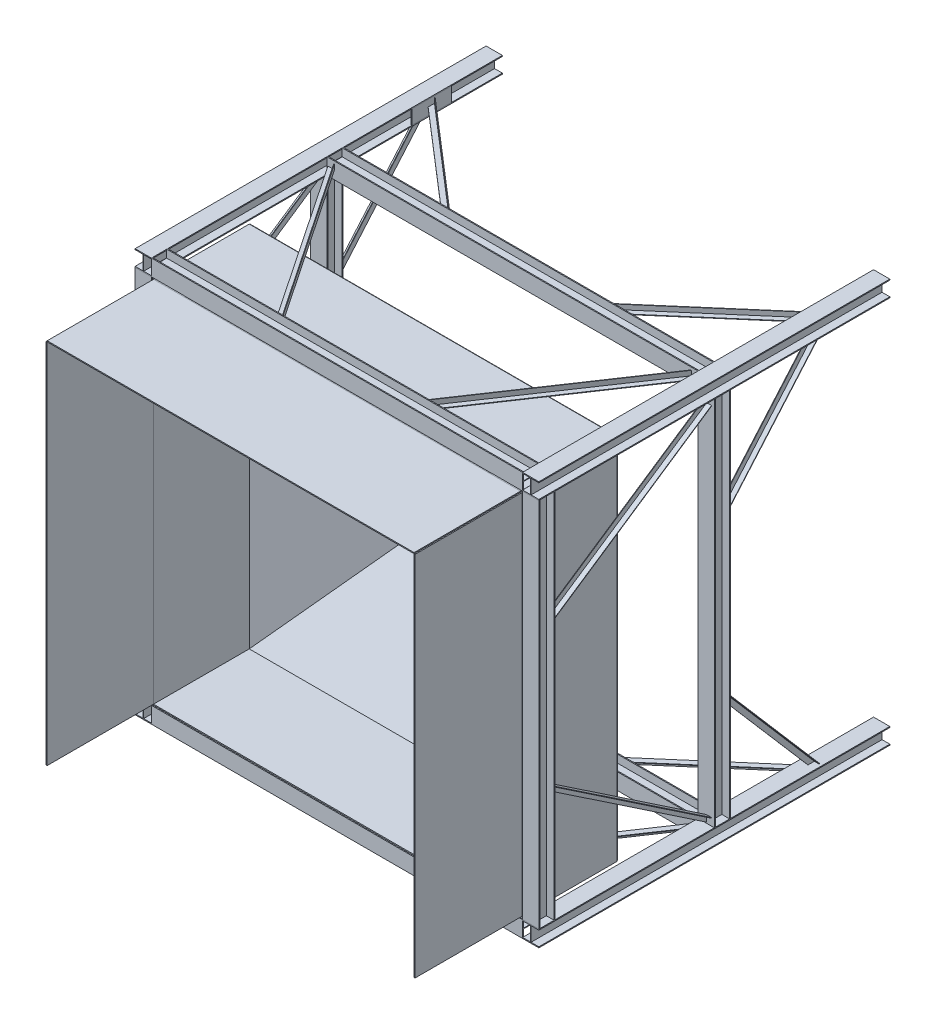
SolidWorks part; units mm, degrees
other "DetailItem1"
other "DetailItem2"
other "DetailItem3"
other "DetailItem4"
other "DetailItem5"
other "DetailItem6"
other "DetailItem7"
other "DetailItem8"
other "DetailItem9"
other "DetailItem10"
other "DetailItem11"
other "DetailItem12"
other "DetailItem13"
other "DetailItem14"
other "DetailItem15"
other "DetailItem16"
other "DetailItem17"
other "DetailItem18"
other "DetailItem19"
other "DetailItem20"
other "DetailItem21"
other "DetailItem22"
other "DetailItem23"
other "DetailItem24"
other "DetailItem25"
other "DetailItem26"
other "DetailItem27"
other "DetailItem28"
other "DetailItem29"
other "DetailItem30"
other "DetailItem31"
other "DetailItem32"
other "DetailItem33"
other "DetailItem34"
other "DetailItem35"
other "DetailItem36"
other "DetailItem37"
other "DetailItem38"
other "DetailItem39"
other "DetailItem40"
other "DetailItem41"
other "DetailItem42"
other "DetailItem43"
other "DetailItem44"
other "DetailItem45"
other "DetailItem46"
other "DetailItem47"
other "DetailItem48"
other "DetailItem49"
other "DetailItem50"
other "DetailItem51"
other "DetailItem52"
other "DetailItem53"
other "DetailItem54"
other "DetailItem55"
other "DetailItem56"
other "DetailItem57"
other "DetailItem58"
other "DetailItem59"
other "DetailItem60"
other "DetailItem61"
other "DetailItem62"
other "DetailItem63"
other "DetailItem64"
other "DetailItem65"
other "DetailItem66"
other "DetailItem67"
other "DetailItem68"
other "DetailItem69"
other "DetailItem70"
other "DetailItem71"
other "DetailItem72"
other "DetailItem73"
other "Carpeta de soldadura"
other "Cordón de soldadura1"
other "Soldadura Viga H carga 1650 B"
other "Soldadura Viga H carga 3300 A"
other "Soldadura Viga H carga 3300 B"
other "Soldadura asiento a tolva carga"
other "Soldadura asiento a bastidor carga"
other "Soldadura Viga H fondo 1650 A"
other "Soldadura Viga H fondo 1650 B"
other "Soldadura Viga H fondo 3300 A"
other "Soldadura Viga H fondo 3300 B"
other "Soldadura asiento a tolva fondo"
other "Soldadura asiento a bastidor fondo"
other "Soldadura Viga H izquierda 1650 A"
other "Soldadura Viga H izquierda 1650 B"
other "Soldadura Viga H izquierda 3300 A"
other "Soldadura Viga H izquierda 3300 B"
other "Soldadura asiento a tolva izquierda"
other "Soldadura asiento a bastidor izquierda"
other "Soldadura Viga H derecha 1650 A"
other "Soldadura Viga H derecha 1650 B"
other "Soldadura Viga H derecha 3300 A"
other "Soldadura Viga H derecha 3300 B"
other "Soldadura asiento a tolva derecha"
other "Soldadura asiento a bastidor derecha"
other "Soldadura Angular superior carga A inferior"
other "Soldadura Angular superior carga A superior"
other "Soldadura Angular inferior carga A inferior"
other "Soldadura Angular inferior carga A superior"
other "Soldadura Angular superior carga B inferior"
other "Soldadura Angular superior carga B superior"
other "Soldadura Angular inferior carga B inferior"
other "Soldadura Angular inferior carga B superior"
other "Soldadura Angular superior fondo A inferior"
other "Soldadura Angular superior fondo A superior"
other "Soldadura Angular inferior fondo A inferior"
other "Soldadura Angular inferior fondo A superior"
other "Soldadura Angular superior fondo B inferior"
other "Soldadura Angular superior fondo B superior"
other "Soldadura Angular inferior fondo B inferior"
other "Soldadura Angular inferior fondo B superior"
other "Soldadura Angular superior izquierda A inferior"
other "Soldadura Angular superior izquierda A superior"
other "Soldadura Angular inferior izquierda A inferior"
other "Soldadura Angular inferior izquierda A superior"
other "Soldadura Angular superior izquierda B inferior"
other "Soldadura Angular superior izquierda B superior"
other "Soldadura Angular inferior izquierda B inferior"
other "Soldadura Angular inferior izquierda B superior"
other "Soldadura Angular superior derecha A inferior"
other "Soldadura Angular superior derecha A superior"
other "Soldadura Angular inferior derecha A inferior"
other "Soldadura Angular inferior derecha A superior"
other "Soldadura Angular superior derecha B inferior"
other "Soldadura Angular superior derecha B superior"
other "Soldadura Angular inferior derecha B inferior"
other "Soldadura Angular inferior derecha B superior"
other "Soldadura esquina del collar carga"
other "Soldadura quiebre del embudo carga"
other "Soldadura arista inclinada carga"
other "Soldadura alerón a collar derecha"
other "Soldadura esquina del collar derecha"
other "Soldadura quiebre del embudo derecha"
other "Soldadura arista inclinada derecha"
other "Soldadura alerón a collar fondo"
other "Soldadura esquina del collar fondo"
other "Soldadura quiebre del embudo fondo"
other "Soldadura arista inclinada fondo"
other "Soldadura alerón a collar izquierda"
other "Soldadura esquina del collar izquierda"
other "Soldadura quiebre del embudo izquierda"
other "Soldadura arista inclinada izquierda"
other "Soldadura esquina alerones derecha"
other "Soldadura esquina alerones izquierda"
material "ASTM A36 Steel"
ref_plane "Front Plane" through (0, 0, 0) normal (0, 0, 1) x (1, 0, 0)
ref_plane "Top Plane" through (0, 0, 0) normal (0, 1, 0) x (1, 0, 0)
ref_plane "Right Plane" through (0, 0, 0) normal (1, 0, 0) x (0, 0, -1)
sketch3d "Referencias 1"
  point P0 (0, 0, 0)
  point P1 (0, -190, 0)
  point P2 (200, 0, 0)
ref_plane "Plano de perfil 1 estructura" through (0, 0, 0) normal (0, 0, 1) x (1, 0, 0)
sketch "Contorno Columna H 1" plane through (0, 0, 0) normal (0, 0, 1) x (1, 0, 0)
  line L0 (-1898, -1898) -> (-1745, -1898)
  line L1 (-1745, -1898) -> (-1745, -1889)
  line L2 (-1745, -1889) -> (-1818.25, -1889)
  line L3 (-1818.25, -1889) -> (-1818.25, -1754)
  line L4 (-1818.25, -1754) -> (-1745, -1754)
  line L5 (-1745, -1754) -> (-1745, -1745)
  line L6 (-1745, -1745) -> (-1898, -1745)
  line L7 (-1898, -1745) -> (-1898, -1754)
  line L8 (-1898, -1754) -> (-1824.75, -1754)
  line L9 (-1824.75, -1754) -> (-1824.75, -1889)
  line L10 (-1824.75, -1889) -> (-1898, -1889)
  line L11 (-1898, -1889) -> (-1898, -1898)
extrude "Columna H 1" add sketch "Contorno Columna H 1" along normal blind 3300 separate body
sketch "Contorno Columna H 2" plane through (0, 0, 0) normal (0, 0, 1) x (1, 0, 0)
  line L0 (-1898, 1745) -> (-1745, 1745)
  line L1 (-1745, 1745) -> (-1745, 1754)
  line L2 (-1745, 1754) -> (-1818.25, 1754)
  line L3 (-1818.25, 1754) -> (-1818.25, 1889)
  line L4 (-1818.25, 1889) -> (-1745, 1889)
  line L5 (-1745, 1889) -> (-1745, 1898)
  line L6 (-1745, 1898) -> (-1898, 1898)
  line L7 (-1898, 1898) -> (-1898, 1889)
  line L8 (-1898, 1889) -> (-1824.75, 1889)
  line L9 (-1824.75, 1889) -> (-1824.75, 1754)
  line L10 (-1824.75, 1754) -> (-1898, 1754)
  line L11 (-1898, 1754) -> (-1898, 1745)
extrude "Columna H 2" add sketch "Contorno Columna H 2" along normal blind 3300 separate body
sketch "Contorno Columna H 3" plane through (0, 0, 0) normal (0, 0, 1) x (1, 0, 0)
  line L0 (1745, -1898) -> (1898, -1898)
  line L1 (1898, -1898) -> (1898, -1889)
  line L2 (1898, -1889) -> (1824.75, -1889)
  line L3 (1824.75, -1889) -> (1824.75, -1754)
  line L4 (1824.75, -1754) -> (1898, -1754)
  line L5 (1898, -1754) -> (1898, -1745)
  line L6 (1898, -1745) -> (1745, -1745)
  line L7 (1745, -1745) -> (1745, -1754)
  line L8 (1745, -1754) -> (1818.25, -1754)
  line L9 (1818.25, -1754) -> (1818.25, -1889)
  line L10 (1818.25, -1889) -> (1745, -1889)
  line L11 (1745, -1889) -> (1745, -1898)
extrude "Columna H 3" add sketch "Contorno Columna H 3" along normal blind 3300 separate body
sketch "Contorno Columna H 4" plane through (0, 0, 0) normal (0, 0, 1) x (1, 0, 0)
  line L0 (1745, 1745) -> (1898, 1745)
  line L1 (1898, 1745) -> (1898, 1754)
  line L2 (1898, 1754) -> (1824.75, 1754)
  line L3 (1824.75, 1754) -> (1824.75, 1889)
  line L4 (1824.75, 1889) -> (1898, 1889)
  line L5 (1898, 1889) -> (1898, 1898)
  line L6 (1898, 1898) -> (1745, 1898)
  line L7 (1745, 1898) -> (1745, 1889)
  line L8 (1745, 1889) -> (1818.25, 1889)
  line L9 (1818.25, 1889) -> (1818.25, 1754)
  line L10 (1818.25, 1754) -> (1745, 1754)
  line L11 (1745, 1754) -> (1745, 1745)
extrude "Columna H 4" add sketch "Contorno Columna H 4" along normal blind 3300 separate body
sketch3d "Referencias 2"
  point P0 (-1745, 0, 0)
  point P1 (-1745, 190, 0)
  point P2 (-1745, 0, 200)
ref_plane "Plano de perfil 2 estructura" through (-1745, 0, 0) normal (1, 0, 0) x (0, 0, -1)
sketch "Contorno Viga H carga 1650" plane through (-1745, 0, 0) normal (1, 0, 0) x (0, 0, -1)
  line L0 (-1497, -1745) -> (-1497, -1898)
  line L1 (-1497, -1898) -> (-1506, -1898)
  line L2 (-1506, -1898) -> (-1506, -1824.75)
  line L3 (-1506, -1824.75) -> (-1641, -1824.75)
  line L4 (-1641, -1824.75) -> (-1641, -1898)
  line L5 (-1641, -1898) -> (-1650, -1898)
  line L6 (-1650, -1898) -> (-1650, -1745)
  line L7 (-1650, -1745) -> (-1641, -1745)
  line L8 (-1641, -1745) -> (-1641, -1818.25)
  line L9 (-1641, -1818.25) -> (-1506, -1818.25)
  line L10 (-1506, -1818.25) -> (-1506, -1745)
  line L11 (-1506, -1745) -> (-1497, -1745)
extrude "Viga H carga 1650" add sketch "Contorno Viga H carga 1650" along normal blind 3490 separate body
sketch "Contorno Viga H carga 3300" plane through (-1745, 0, 0) normal (1, 0, 0) x (0, 0, -1)
  line L0 (-3147, -1745) -> (-3147, -1898)
  line L1 (-3147, -1898) -> (-3156, -1898)
  line L2 (-3156, -1898) -> (-3156, -1824.75)
  line L3 (-3156, -1824.75) -> (-3291, -1824.75)
  line L4 (-3291, -1824.75) -> (-3291, -1898)
  line L5 (-3291, -1898) -> (-3300, -1898)
  line L6 (-3300, -1898) -> (-3300, -1745)
  line L7 (-3300, -1745) -> (-3291, -1745)
  line L8 (-3291, -1745) -> (-3291, -1818.25)
  line L9 (-3291, -1818.25) -> (-3156, -1818.25)
  line L10 (-3156, -1818.25) -> (-3156, -1745)
  line L11 (-3156, -1745) -> (-3147, -1745)
extrude "Viga H carga 3300" add sketch "Contorno Viga H carga 3300" along normal blind 3490 separate body
sketch "Contorno Cierre columna carga A" plane through (-1745, 0, 0) normal (1, 0, 0) x (0, 0, -1)
  line L0 (-480, -1754) -> (-480, -1889)
  line L1 (-480, -1889) -> (-850, -1889)
  line L2 (-850, -1889) -> (-850, -1754)
  line L3 (-850, -1754) -> (-480, -1754)
extrude "Cierre columna carga A" add sketch "Contorno Cierre columna carga A" against normal blind 8 separate body
sketch3d "Referencias 3"
  point P0 (0, -1821.5, 0)
  point P1 (-190, -1821.5, 0)
  point P2 (0, -1821.5, 200)
ref_plane "Plano de perfil 3 estructura" through (0, -1821.5, 0) normal (0, 1, 0) x (1, 0, 0)
sketch "Contorno Ala plana Angular superior carga A" plane through (0, -1821.5, 0) normal (0, 1, 0) x (1, 0, 0)
  line L0 (-1674.8701, -1650) -> (-1735.1299, -1650)
  line L1 (-1735.1299, -1650) -> (-728.1299, -3147)
  line L2 (-728.1299, -3147) -> (-667.8701, -3147)
  line L3 (-667.8701, -3147) -> (-1674.8701, -1650)
extrude "Ala plana Angular superior carga A" add sketch "Contorno Ala plana Angular superior carga A" against normal blind 5 separate body
sketch3d "Referencias 4"
  point P0 (0, -1826.5, 0)
  point P1 (-190, -1826.5, 0)
  point P2 (0, -1826.5, 200)
ref_plane "Plano de perfil 4 estructura" through (0, -1826.5, 0) normal (0, 1, 0) x (1, 0, 0)
sketch "Contorno Retorno Angular superior carga A" plane through (0, -1826.5, 0) normal (0, 1, 0) x (1, 0, 0)
  line L0 (-1674.8701, -1650) -> (-1680.8961, -1650)
  line L1 (-1680.8961, -1650) -> (-673.8961, -3147)
  line L2 (-673.8961, -3147) -> (-667.8701, -3147)
  line L3 (-667.8701, -3147) -> (-1674.8701, -1650)
extrude "Retorno Angular superior carga A" add sketch "Contorno Retorno Angular superior carga A" against normal blind 45 separate body
combine bodies "Angular superior carga A" operation type add bodies to combine 108 109
sketch "Contorno Ala plana Angular inferior carga A" plane through (0, -1821.5, 0) normal (0, 1, 0) x (1, 0, 0)
  line L0 (-1745, -631.991) -> (-1745, -698.009)
  line L1 (-1745, -698.009) -> (-818.2856, -1497)
  line L2 (-818.2856, -1497) -> (-741.7144, -1497)
  line L3 (-741.7144, -1497) -> (-1745, -631.991)
extrude "Ala plana Angular inferior carga A" add sketch "Contorno Ala plana Angular inferior carga A" against normal blind 5 separate body
sketch "Contorno Retorno Angular inferior carga A" plane through (0, -1826.5, 0) normal (0, 1, 0) x (1, 0, 0)
  line L0 (-1745, -631.991) -> (-1745, -638.5928)
  line L1 (-1745, -638.5928) -> (-749.3715, -1497)
  line L2 (-749.3715, -1497) -> (-741.7144, -1497)
  line L3 (-741.7144, -1497) -> (-1745, -631.991)
extrude "Retorno Angular inferior carga A" add sketch "Contorno Retorno Angular inferior carga A" against normal blind 45 separate body
combine bodies "Angular inferior carga A" operation type add bodies to combine 111 112
sketch3d "Referencias 5"
  point P0 (1745, 0, 0)
  point P1 (1745, 190, 0)
  point P2 (1745, 0, 200)
ref_plane "Plano de perfil 5 estructura" through (1745, 0, 0) normal (1, 0, 0) x (0, 0, -1)
sketch "Contorno Cierre columna carga B" plane through (1745, 0, 0) normal (1, 0, 0) x (0, 0, -1)
  line L0 (-480, -1754) -> (-480, -1889)
  line L1 (-480, -1889) -> (-850, -1889)
  line L2 (-850, -1889) -> (-850, -1754)
  line L3 (-850, -1754) -> (-480, -1754)
extrude "Cierre columna carga B" add sketch "Contorno Cierre columna carga B" along normal blind 8 separate body
sketch "Contorno Ala plana Angular superior carga B" plane through (0, -1821.5, 0) normal (0, 1, 0) x (1, 0, 0)
  line L0 (1674.8701, -1650) -> (1735.1299, -1650)
  line L1 (1735.1299, -1650) -> (728.1299, -3147)
  line L2 (728.1299, -3147) -> (667.8701, -3147)
  line L3 (667.8701, -3147) -> (1674.8701, -1650)
extrude "Ala plana Angular superior carga B" add sketch "Contorno Ala plana Angular superior carga B" against normal blind 5 separate body
sketch "Contorno Retorno Angular superior carga B" plane through (0, -1826.5, 0) normal (0, 1, 0) x (1, 0, 0)
  line L0 (1674.8701, -1650) -> (1680.8961, -1650)
  line L1 (1680.8961, -1650) -> (673.8961, -3147)
  line L2 (673.8961, -3147) -> (667.8701, -3147)
  line L3 (667.8701, -3147) -> (1674.8701, -1650)
extrude "Retorno Angular superior carga B" add sketch "Contorno Retorno Angular superior carga B" against normal blind 45 separate body
combine bodies "Angular superior carga B" operation type add bodies to combine 115 116
sketch "Contorno Ala plana Angular inferior carga B" plane through (0, -1821.5, 0) normal (0, 1, 0) x (1, 0, 0)
  line L0 (1745, -631.991) -> (1745, -698.009)
  line L1 (1745, -698.009) -> (818.2856, -1497)
  line L2 (818.2856, -1497) -> (741.7144, -1497)
  line L3 (741.7144, -1497) -> (1745, -631.991)
extrude "Ala plana Angular inferior carga B" add sketch "Contorno Ala plana Angular inferior carga B" against normal blind 5 separate body
sketch "Contorno Retorno Angular inferior carga B" plane through (0, -1826.5, 0) normal (0, 1, 0) x (1, 0, 0)
  line L0 (1745, -631.991) -> (1745, -638.5928)
  line L1 (1745, -638.5928) -> (749.3715, -1497)
  line L2 (749.3715, -1497) -> (741.7144, -1497)
  line L3 (741.7144, -1497) -> (1745, -631.991)
extrude "Retorno Angular inferior carga B" add sketch "Contorno Retorno Angular inferior carga B" against normal blind 45 separate body
combine bodies "Angular inferior carga B" operation type add bodies to combine 118 119
sketch3d "Referencias 6"
  point P0 (0, 0, 3281.475)
  point P1 (0, -190, 3281.475)
  point P2 (200, 0, 3281.475)
ref_plane "Plano de perfil 6 estructura" through (0, 0, 3281.475) normal (0, 0, 1) x (1, 0, 0)
sketch "Contorno Asiento soldado carga" plane through (0, 0, 3281.475) normal (0, 0, 1) x (1, 0, 0)
  line L0 (-1450, -1734.525) -> (1450, -1734.525)
  line L1 (1450, -1734.525) -> (1450, -1818.25)
  line L2 (1450, -1818.25) -> (-1450, -1818.25)
  line L3 (-1450, -1818.25) -> (-1450, -1734.525)
extrude "Asiento soldado carga" add sketch "Contorno Asiento soldado carga" along normal blind 9.525 separate body
sketch "Contorno Viga H fondo 1650" plane through (-1745, 0, 0) normal (1, 0, 0) x (0, 0, -1)
  line L0 (-1497, 1745) -> (-1497, 1898)
  line L1 (-1497, 1898) -> (-1506, 1898)
  line L2 (-1506, 1898) -> (-1506, 1824.75)
  line L3 (-1506, 1824.75) -> (-1641, 1824.75)
  line L4 (-1641, 1824.75) -> (-1641, 1898)
  line L5 (-1641, 1898) -> (-1650, 1898)
  line L6 (-1650, 1898) -> (-1650, 1745)
  line L7 (-1650, 1745) -> (-1641, 1745)
  line L8 (-1641, 1745) -> (-1641, 1818.25)
  line L9 (-1641, 1818.25) -> (-1506, 1818.25)
  line L10 (-1506, 1818.25) -> (-1506, 1745)
  line L11 (-1506, 1745) -> (-1497, 1745)
extrude "Viga H fondo 1650" add sketch "Contorno Viga H fondo 1650" along normal blind 3490 separate body
sketch "Contorno Viga H fondo 3300" plane through (-1745, 0, 0) normal (1, 0, 0) x (0, 0, -1)
  line L0 (-3147, 1745) -> (-3147, 1898)
  line L1 (-3147, 1898) -> (-3156, 1898)
  line L2 (-3156, 1898) -> (-3156, 1824.75)
  line L3 (-3156, 1824.75) -> (-3291, 1824.75)
  line L4 (-3291, 1824.75) -> (-3291, 1898)
  line L5 (-3291, 1898) -> (-3300, 1898)
  line L6 (-3300, 1898) -> (-3300, 1745)
  line L7 (-3300, 1745) -> (-3291, 1745)
  line L8 (-3291, 1745) -> (-3291, 1818.25)
  line L9 (-3291, 1818.25) -> (-3156, 1818.25)
  line L10 (-3156, 1818.25) -> (-3156, 1745)
  line L11 (-3156, 1745) -> (-3147, 1745)
extrude "Viga H fondo 3300" add sketch "Contorno Viga H fondo 3300" along normal blind 3490 separate body
sketch "Contorno Cierre columna fondo A" plane through (-1745, 0, 0) normal (1, 0, 0) x (0, 0, -1)
  line L0 (-480, 1754) -> (-480, 1889)
  line L1 (-480, 1889) -> (-850, 1889)
  line L2 (-850, 1889) -> (-850, 1754)
  line L3 (-850, 1754) -> (-480, 1754)
extrude "Cierre columna fondo A" add sketch "Contorno Cierre columna fondo A" against normal blind 8 separate body
sketch3d "Referencias 7"
  point P0 (0, 1821.5, 0)
  point P1 (-190, 1821.5, 0)
  point P2 (0, 1821.5, 200)
ref_plane "Plano de perfil 7 estructura" through (0, 1821.5, 0) normal (0, 1, 0) x (1, 0, 0)
sketch "Contorno Ala plana Angular superior fondo A" plane through (0, 1821.5, 0) normal (0, 1, 0) x (1, 0, 0)
  line L0 (-1674.8701, -1650) -> (-1735.1299, -1650)
  line L1 (-1735.1299, -1650) -> (-728.1299, -3147)
  line L2 (-728.1299, -3147) -> (-667.8701, -3147)
  line L3 (-667.8701, -3147) -> (-1674.8701, -1650)
extrude "Ala plana Angular superior fondo A" add sketch "Contorno Ala plana Angular superior fondo A" along normal blind 5 separate body
sketch3d "Referencias 8"
  point P0 (0, 1826.5, 0)
  point P1 (-190, 1826.5, 0)
  point P2 (0, 1826.5, 200)
ref_plane "Plano de perfil 8 estructura" through (0, 1826.5, 0) normal (0, 1, 0) x (1, 0, 0)
sketch "Contorno Retorno Angular superior fondo A" plane through (0, 1826.5, 0) normal (0, 1, 0) x (1, 0, 0)
  line L0 (-1674.8701, -1650) -> (-1680.8961, -1650)
  line L1 (-1680.8961, -1650) -> (-673.8961, -3147)
  line L2 (-673.8961, -3147) -> (-667.8701, -3147)
  line L3 (-667.8701, -3147) -> (-1674.8701, -1650)
extrude "Retorno Angular superior fondo A" add sketch "Contorno Retorno Angular superior fondo A" along normal blind 45 separate body
combine bodies "Angular superior fondo A" operation type add bodies to combine 125 126
sketch "Contorno Ala plana Angular inferior fondo A" plane through (0, 1821.5, 0) normal (0, 1, 0) x (1, 0, 0)
  line L0 (-1745, -631.991) -> (-1745, -698.009)
  line L1 (-1745, -698.009) -> (-818.2856, -1497)
  line L2 (-818.2856, -1497) -> (-741.7144, -1497)
  line L3 (-741.7144, -1497) -> (-1745, -631.991)
extrude "Ala plana Angular inferior fondo A" add sketch "Contorno Ala plana Angular inferior fondo A" along normal blind 5 separate body
sketch "Contorno Retorno Angular inferior fondo A" plane through (0, 1826.5, 0) normal (0, 1, 0) x (1, 0, 0)
  line L0 (-1745, -631.991) -> (-1745, -638.5928)
  line L1 (-1745, -638.5928) -> (-749.3715, -1497)
  line L2 (-749.3715, -1497) -> (-741.7144, -1497)
  line L3 (-741.7144, -1497) -> (-1745, -631.991)
extrude "Retorno Angular inferior fondo A" add sketch "Contorno Retorno Angular inferior fondo A" along normal blind 45 separate body
combine bodies "Angular inferior fondo A" operation type add bodies to combine 128 129
sketch "Contorno Cierre columna fondo B" plane through (1745, 0, 0) normal (1, 0, 0) x (0, 0, -1)
  line L0 (-480, 1754) -> (-480, 1889)
  line L1 (-480, 1889) -> (-850, 1889)
  line L2 (-850, 1889) -> (-850, 1754)
  line L3 (-850, 1754) -> (-480, 1754)
extrude "Cierre columna fondo B" add sketch "Contorno Cierre columna fondo B" along normal blind 8 separate body
sketch "Contorno Ala plana Angular superior fondo B" plane through (0, 1821.5, 0) normal (0, 1, 0) x (1, 0, 0)
  line L0 (1674.8701, -1650) -> (1735.1299, -1650)
  line L1 (1735.1299, -1650) -> (728.1299, -3147)
  line L2 (728.1299, -3147) -> (667.8701, -3147)
  line L3 (667.8701, -3147) -> (1674.8701, -1650)
extrude "Ala plana Angular superior fondo B" add sketch "Contorno Ala plana Angular superior fondo B" along normal blind 5 separate body
sketch "Contorno Retorno Angular superior fondo B" plane through (0, 1826.5, 0) normal (0, 1, 0) x (1, 0, 0)
  line L0 (1674.8701, -1650) -> (1680.8961, -1650)
  line L1 (1680.8961, -1650) -> (673.8961, -3147)
  line L2 (673.8961, -3147) -> (667.8701, -3147)
  line L3 (667.8701, -3147) -> (1674.8701, -1650)
extrude "Retorno Angular superior fondo B" add sketch "Contorno Retorno Angular superior fondo B" along normal blind 45 separate body
combine bodies "Angular superior fondo B" operation type add bodies to combine 132 133
sketch "Contorno Ala plana Angular inferior fondo B" plane through (0, 1821.5, 0) normal (0, 1, 0) x (1, 0, 0)
  line L0 (1745, -631.991) -> (1745, -698.009)
  line L1 (1745, -698.009) -> (818.2856, -1497)
  line L2 (818.2856, -1497) -> (741.7144, -1497)
  line L3 (741.7144, -1497) -> (1745, -631.991)
extrude "Ala plana Angular inferior fondo B" add sketch "Contorno Ala plana Angular inferior fondo B" along normal blind 5 separate body
sketch "Contorno Retorno Angular inferior fondo B" plane through (0, 1826.5, 0) normal (0, 1, 0) x (1, 0, 0)
  line L0 (1745, -631.991) -> (1745, -638.5928)
  line L1 (1745, -638.5928) -> (749.3715, -1497)
  line L2 (749.3715, -1497) -> (741.7144, -1497)
  line L3 (741.7144, -1497) -> (1745, -631.991)
extrude "Retorno Angular inferior fondo B" add sketch "Contorno Retorno Angular inferior fondo B" along normal blind 45 separate body
combine bodies "Angular inferior fondo B" operation type add bodies to combine 135 136
sketch "Contorno Asiento soldado fondo" plane through (0, 0, 3281.475) normal (0, 0, 1) x (1, 0, 0)
  line L0 (-1450, 1734.525) -> (1450, 1734.525)
  line L1 (1450, 1734.525) -> (1450, 1818.25)
  line L2 (1450, 1818.25) -> (-1450, 1818.25)
  line L3 (-1450, 1818.25) -> (-1450, 1734.525)
extrude "Asiento soldado fondo" add sketch "Contorno Asiento soldado fondo" along normal blind 9.525 separate body
sketch3d "Referencias 9"
  point P0 (0, -1745, 0)
  point P1 (-190, -1745, 0)
  point P2 (0, -1745, 200)
ref_plane "Plano de perfil 9 estructura" through (0, -1745, 0) normal (0, 1, 0) x (1, 0, 0)
sketch "Contorno Viga H izquierda 1650" plane through (0, -1745, 0) normal (0, 1, 0) x (1, 0, 0)
  line L0 (-1745, -1497) -> (-1898, -1497)
  line L1 (-1898, -1497) -> (-1898, -1506)
  line L2 (-1898, -1506) -> (-1824.75, -1506)
  line L3 (-1824.75, -1506) -> (-1824.75, -1641)
  line L4 (-1824.75, -1641) -> (-1898, -1641)
  line L5 (-1898, -1641) -> (-1898, -1650)
  line L6 (-1898, -1650) -> (-1745, -1650)
  line L7 (-1745, -1650) -> (-1745, -1641)
  line L8 (-1745, -1641) -> (-1818.25, -1641)
  line L9 (-1818.25, -1641) -> (-1818.25, -1506)
  line L10 (-1818.25, -1506) -> (-1745, -1506)
  line L11 (-1745, -1506) -> (-1745, -1497)
extrude "Viga H izquierda 1650" add sketch "Contorno Viga H izquierda 1650" along normal blind 3490 separate body
sketch "Contorno Viga H izquierda 3300" plane through (0, -1745, 0) normal (0, 1, 0) x (1, 0, 0)
  line L0 (-1745, -3147) -> (-1898, -3147)
  line L1 (-1898, -3147) -> (-1898, -3156)
  line L2 (-1898, -3156) -> (-1824.75, -3156)
  line L3 (-1824.75, -3156) -> (-1824.75, -3291)
  line L4 (-1824.75, -3291) -> (-1898, -3291)
  line L5 (-1898, -3291) -> (-1898, -3300)
  line L6 (-1898, -3300) -> (-1745, -3300)
  line L7 (-1745, -3300) -> (-1745, -3291)
  line L8 (-1745, -3291) -> (-1818.25, -3291)
  line L9 (-1818.25, -3291) -> (-1818.25, -3156)
  line L10 (-1818.25, -3156) -> (-1745, -3156)
  line L11 (-1745, -3156) -> (-1745, -3147)
extrude "Viga H izquierda 3300" add sketch "Contorno Viga H izquierda 3300" along normal blind 3490 separate body
sketch3d "Referencias 10"
  point P0 (-1821.5, 0, 0)
  point P1 (-1821.5, 190, 0)
  point P2 (-1821.5, 0, 200)
ref_plane "Plano de perfil 10 estructura" through (-1821.5, 0, 0) normal (1, 0, 0) x (0, 0, -1)
sketch "Contorno Ala plana Angular superior izquierda A" plane through (-1821.5, 0, 0) normal (1, 0, 0) x (0, 0, -1)
  line L0 (-1650, -1674.8701) -> (-1650, -1735.1299)
  line L1 (-1650, -1735.1299) -> (-3147, -728.1299)
  line L2 (-3147, -728.1299) -> (-3147, -667.8701)
  line L3 (-3147, -667.8701) -> (-1650, -1674.8701)
extrude "Ala plana Angular superior izquierda A" add sketch "Contorno Ala plana Angular superior izquierda A" against normal blind 5 separate body
sketch3d "Referencias 11"
  point P0 (-1826.5, 0, 0)
  point P1 (-1826.5, 190, 0)
  point P2 (-1826.5, 0, 200)
ref_plane "Plano de perfil 11 estructura" through (-1826.5, 0, 0) normal (1, 0, 0) x (0, 0, -1)
sketch "Contorno Retorno Angular superior izquierda A" plane through (-1826.5, 0, 0) normal (1, 0, 0) x (0, 0, -1)
  line L0 (-1650, -1674.8701) -> (-1650, -1680.8961)
  line L1 (-1650, -1680.8961) -> (-3147, -673.8961)
  line L2 (-3147, -673.8961) -> (-3147, -667.8701)
  line L3 (-3147, -667.8701) -> (-1650, -1674.8701)
extrude "Retorno Angular superior izquierda A" add sketch "Contorno Retorno Angular superior izquierda A" against normal blind 45 separate body
combine bodies "Angular superior izquierda A" operation type add bodies to combine 141 142
sketch "Contorno Ala plana Angular inferior izquierda A" plane through (-1821.5, 0, 0) normal (1, 0, 0) x (0, 0, -1)
  line L0 (-631.991, -1745) -> (-698.009, -1745)
  line L1 (-698.009, -1745) -> (-1497, -818.2856)
  line L2 (-1497, -818.2856) -> (-1497, -741.7144)
  line L3 (-1497, -741.7144) -> (-631.991, -1745)
extrude "Ala plana Angular inferior izquierda A" add sketch "Contorno Ala plana Angular inferior izquierda A" against normal blind 5 separate body
sketch "Contorno Retorno Angular inferior izquierda A" plane through (-1826.5, 0, 0) normal (1, 0, 0) x (0, 0, -1)
  line L0 (-631.991, -1745) -> (-638.5928, -1745)
  line L1 (-638.5928, -1745) -> (-1497, -749.3715)
  line L2 (-1497, -749.3715) -> (-1497, -741.7144)
  line L3 (-1497, -741.7144) -> (-631.991, -1745)
extrude "Retorno Angular inferior izquierda A" add sketch "Contorno Retorno Angular inferior izquierda A" against normal blind 45 separate body
combine bodies "Angular inferior izquierda A" operation type add bodies to combine 144 145
sketch "Contorno Ala plana Angular superior izquierda B" plane through (-1821.5, 0, 0) normal (1, 0, 0) x (0, 0, -1)
  line L0 (-1650, 1674.8701) -> (-1650, 1735.1299)
  line L1 (-1650, 1735.1299) -> (-3147, 728.1299)
  line L2 (-3147, 728.1299) -> (-3147, 667.8701)
  line L3 (-3147, 667.8701) -> (-1650, 1674.8701)
extrude "Ala plana Angular superior izquierda B" add sketch "Contorno Ala plana Angular superior izquierda B" against normal blind 5 separate body
sketch "Contorno Retorno Angular superior izquierda B" plane through (-1826.5, 0, 0) normal (1, 0, 0) x (0, 0, -1)
  line L0 (-1650, 1674.8701) -> (-1650, 1680.8961)
  line L1 (-1650, 1680.8961) -> (-3147, 673.8961)
  line L2 (-3147, 673.8961) -> (-3147, 667.8701)
  line L3 (-3147, 667.8701) -> (-1650, 1674.8701)
extrude "Retorno Angular superior izquierda B" add sketch "Contorno Retorno Angular superior izquierda B" against normal blind 45 separate body
combine bodies "Angular superior izquierda B" operation type add bodies to combine 147 148
sketch "Contorno Ala plana Angular inferior izquierda B" plane through (-1821.5, 0, 0) normal (1, 0, 0) x (0, 0, -1)
  line L0 (-631.991, 1745) -> (-698.009, 1745)
  line L1 (-698.009, 1745) -> (-1497, 818.2856)
  line L2 (-1497, 818.2856) -> (-1497, 741.7144)
  line L3 (-1497, 741.7144) -> (-631.991, 1745)
extrude "Ala plana Angular inferior izquierda B" add sketch "Contorno Ala plana Angular inferior izquierda B" against normal blind 5 separate body
sketch "Contorno Retorno Angular inferior izquierda B" plane through (-1826.5, 0, 0) normal (1, 0, 0) x (0, 0, -1)
  line L0 (-631.991, 1745) -> (-638.5928, 1745)
  line L1 (-638.5928, 1745) -> (-1497, 749.3715)
  line L2 (-1497, 749.3715) -> (-1497, 741.7144)
  line L3 (-1497, 741.7144) -> (-631.991, 1745)
extrude "Retorno Angular inferior izquierda B" add sketch "Contorno Retorno Angular inferior izquierda B" against normal blind 45 separate body
combine bodies "Angular inferior izquierda B" operation type add bodies to combine 150 151
sketch "Contorno Asiento soldado izquierda" plane through (0, 0, 3281.475) normal (0, 0, 1) x (1, 0, 0)
  line L0 (-1734.525, -1450) -> (-1734.525, 1450)
  line L1 (-1734.525, 1450) -> (-1818.25, 1450)
  line L2 (-1818.25, 1450) -> (-1818.25, -1450)
  line L3 (-1818.25, -1450) -> (-1734.525, -1450)
extrude "Asiento soldado izquierda" add sketch "Contorno Asiento soldado izquierda" along normal blind 9.525 separate body
sketch "Contorno Viga H derecha 1650" plane through (0, -1745, 0) normal (0, 1, 0) x (1, 0, 0)
  line L0 (1745, -1497) -> (1898, -1497)
  line L1 (1898, -1497) -> (1898, -1506)
  line L2 (1898, -1506) -> (1824.75, -1506)
  line L3 (1824.75, -1506) -> (1824.75, -1641)
  line L4 (1824.75, -1641) -> (1898, -1641)
  line L5 (1898, -1641) -> (1898, -1650)
  line L6 (1898, -1650) -> (1745, -1650)
  line L7 (1745, -1650) -> (1745, -1641)
  line L8 (1745, -1641) -> (1818.25, -1641)
  line L9 (1818.25, -1641) -> (1818.25, -1506)
  line L10 (1818.25, -1506) -> (1745, -1506)
  line L11 (1745, -1506) -> (1745, -1497)
extrude "Viga H derecha 1650" add sketch "Contorno Viga H derecha 1650" along normal blind 3490 separate body
sketch "Contorno Viga H derecha 3300" plane through (0, -1745, 0) normal (0, 1, 0) x (1, 0, 0)
  line L0 (1745, -3147) -> (1898, -3147)
  line L1 (1898, -3147) -> (1898, -3156)
  line L2 (1898, -3156) -> (1824.75, -3156)
  line L3 (1824.75, -3156) -> (1824.75, -3291)
  line L4 (1824.75, -3291) -> (1898, -3291)
  line L5 (1898, -3291) -> (1898, -3300)
  line L6 (1898, -3300) -> (1745, -3300)
  line L7 (1745, -3300) -> (1745, -3291)
  line L8 (1745, -3291) -> (1818.25, -3291)
  line L9 (1818.25, -3291) -> (1818.25, -3156)
  line L10 (1818.25, -3156) -> (1745, -3156)
  line L11 (1745, -3156) -> (1745, -3147)
extrude "Viga H derecha 3300" add sketch "Contorno Viga H derecha 3300" along normal blind 3490 separate body
sketch3d "Referencias 12"
  point P0 (1821.5, 0, 0)
  point P1 (1821.5, 190, 0)
  point P2 (1821.5, 0, 200)
ref_plane "Plano de perfil 12 estructura" through (1821.5, 0, 0) normal (1, 0, 0) x (0, 0, -1)
sketch "Contorno Ala plana Angular superior derecha A" plane through (1821.5, 0, 0) normal (1, 0, 0) x (0, 0, -1)
  line L0 (-1650, -1674.8701) -> (-1650, -1735.1299)
  line L1 (-1650, -1735.1299) -> (-3147, -728.1299)
  line L2 (-3147, -728.1299) -> (-3147, -667.8701)
  line L3 (-3147, -667.8701) -> (-1650, -1674.8701)
extrude "Ala plana Angular superior derecha A" add sketch "Contorno Ala plana Angular superior derecha A" along normal blind 5 separate body
sketch3d "Referencias 13"
  point P0 (1826.5, 0, 0)
  point P1 (1826.5, 190, 0)
  point P2 (1826.5, 0, 200)
ref_plane "Plano de perfil 13 estructura" through (1826.5, 0, 0) normal (1, 0, 0) x (0, 0, -1)
sketch "Contorno Retorno Angular superior derecha A" plane through (1826.5, 0, 0) normal (1, 0, 0) x (0, 0, -1)
  line L0 (-1650, -1674.8701) -> (-1650, -1680.8961)
  line L1 (-1650, -1680.8961) -> (-3147, -673.8961)
  line L2 (-3147, -673.8961) -> (-3147, -667.8701)
  line L3 (-3147, -667.8701) -> (-1650, -1674.8701)
extrude "Retorno Angular superior derecha A" add sketch "Contorno Retorno Angular superior derecha A" along normal blind 45 separate body
combine bodies "Angular superior derecha A" operation type add bodies to combine 156 157
sketch "Contorno Ala plana Angular inferior derecha A" plane through (1821.5, 0, 0) normal (1, 0, 0) x (0, 0, -1)
  line L0 (-631.991, -1745) -> (-698.009, -1745)
  line L1 (-698.009, -1745) -> (-1497, -818.2856)
  line L2 (-1497, -818.2856) -> (-1497, -741.7144)
  line L3 (-1497, -741.7144) -> (-631.991, -1745)
extrude "Ala plana Angular inferior derecha A" add sketch "Contorno Ala plana Angular inferior derecha A" along normal blind 5 separate body
sketch "Contorno Retorno Angular inferior derecha A" plane through (1826.5, 0, 0) normal (1, 0, 0) x (0, 0, -1)
  line L0 (-631.991, -1745) -> (-638.5928, -1745)
  line L1 (-638.5928, -1745) -> (-1497, -749.3715)
  line L2 (-1497, -749.3715) -> (-1497, -741.7144)
  line L3 (-1497, -741.7144) -> (-631.991, -1745)
extrude "Retorno Angular inferior derecha A" add sketch "Contorno Retorno Angular inferior derecha A" along normal blind 45 separate body
combine bodies "Angular inferior derecha A" operation type add bodies to combine 159 160
sketch "Contorno Ala plana Angular superior derecha B" plane through (1821.5, 0, 0) normal (1, 0, 0) x (0, 0, -1)
  line L0 (-1650, 1674.8701) -> (-1650, 1735.1299)
  line L1 (-1650, 1735.1299) -> (-3147, 728.1299)
  line L2 (-3147, 728.1299) -> (-3147, 667.8701)
  line L3 (-3147, 667.8701) -> (-1650, 1674.8701)
extrude "Ala plana Angular superior derecha B" add sketch "Contorno Ala plana Angular superior derecha B" along normal blind 5 separate body
sketch "Contorno Retorno Angular superior derecha B" plane through (1826.5, 0, 0) normal (1, 0, 0) x (0, 0, -1)
  line L0 (-1650, 1674.8701) -> (-1650, 1680.8961)
  line L1 (-1650, 1680.8961) -> (-3147, 673.8961)
  line L2 (-3147, 673.8961) -> (-3147, 667.8701)
  line L3 (-3147, 667.8701) -> (-1650, 1674.8701)
extrude "Retorno Angular superior derecha B" add sketch "Contorno Retorno Angular superior derecha B" along normal blind 45 separate body
combine bodies "Angular superior derecha B" operation type add bodies to combine 162 163
sketch "Contorno Ala plana Angular inferior derecha B" plane through (1821.5, 0, 0) normal (1, 0, 0) x (0, 0, -1)
  line L0 (-631.991, 1745) -> (-698.009, 1745)
  line L1 (-698.009, 1745) -> (-1497, 818.2856)
  line L2 (-1497, 818.2856) -> (-1497, 741.7144)
  line L3 (-1497, 741.7144) -> (-631.991, 1745)
extrude "Ala plana Angular inferior derecha B" add sketch "Contorno Ala plana Angular inferior derecha B" along normal blind 5 separate body
sketch "Contorno Retorno Angular inferior derecha B" plane through (1826.5, 0, 0) normal (1, 0, 0) x (0, 0, -1)
  line L0 (-631.991, 1745) -> (-638.5928, 1745)
  line L1 (-638.5928, 1745) -> (-1497, 749.3715)
  line L2 (-1497, 749.3715) -> (-1497, 741.7144)
  line L3 (-1497, 741.7144) -> (-631.991, 1745)
extrude "Retorno Angular inferior derecha B" add sketch "Contorno Retorno Angular inferior derecha B" along normal blind 45 separate body
combine bodies "Angular inferior derecha B" operation type add bodies to combine 165 166
sketch "Contorno Asiento soldado derecha" plane through (0, 0, 3281.475) normal (0, 0, 1) x (1, 0, 0)
  line L0 (1734.525, -1450) -> (1734.525, 1450)
  line L1 (1734.525, 1450) -> (1818.25, 1450)
  line L2 (1818.25, 1450) -> (1818.25, -1450)
  line L3 (1818.25, -1450) -> (1734.525, -1450)
extrude "Asiento soldado derecha" add sketch "Contorno Asiento soldado derecha" along normal blind 9.525 separate body
sketch3d "Junta Viga H carga 1650 A"
  line L0 (-1745, -1745, 1650) -> (-1745, -1898, 1650)
sketch3d "Junta Viga H carga 1650 B"
  line L0 (1745, -1745, 1650) -> (1745, -1898, 1650)
sketch3d "Junta Viga H carga 3300 A"
  line L0 (-1745, -1745, 3300) -> (-1745, -1898, 3300)
sketch3d "Junta Viga H carga 3300 B"
  line L0 (1745, -1745, 3300) -> (1745, -1898, 3300)
sketch3d "Junta Angular superior carga A inferior"
  line L0 (-1674.8701, -1821.5, 1650) -> (-1735.1299, -1821.5, 1650)
sketch3d "Junta Angular superior carga A superior"
  line L0 (-667.8701, -1821.5, 3147) -> (-728.1299, -1821.5, 3147)
sketch3d "Junta Angular inferior carga A inferior"
  line L0 (-1745, -1821.5, 631.991) -> (-1745, -1821.5, 698.009)
sketch3d "Junta Angular inferior carga A superior"
  line L0 (-741.7144, -1821.5, 1497) -> (-818.2856, -1821.5, 1497)
sketch3d "Junta Angular superior carga B inferior"
  line L0 (1674.8701, -1821.5, 1650) -> (1735.1299, -1821.5, 1650)
sketch3d "Junta Angular superior carga B superior"
  line L0 (667.8701, -1821.5, 3147) -> (728.1299, -1821.5, 3147)
sketch3d "Junta Angular inferior carga B inferior"
  line L0 (1745, -1821.5, 631.991) -> (1745, -1821.5, 698.009)
sketch3d "Junta Angular inferior carga B superior"
  line L0 (741.7144, -1821.5, 1497) -> (818.2856, -1821.5, 1497)
sketch3d "Junta asiento a tolva carga"
  line L0 (-1450, -1734.525, 3281.475) -> (1450, -1734.525, 3281.475)
sketch3d "Junta asiento a bastidor carga"
  line L0 (-1450, -1745, 3291) -> (1450, -1745, 3291)
sketch3d "Junta Viga H fondo 1650 A"
  line L0 (-1745, 1745, 1650) -> (-1745, 1898, 1650)
sketch3d "Junta Viga H fondo 1650 B"
  line L0 (1745, 1745, 1650) -> (1745, 1898, 1650)
sketch3d "Junta Viga H fondo 3300 A"
  line L0 (-1745, 1745, 3300) -> (-1745, 1898, 3300)
sketch3d "Junta Viga H fondo 3300 B"
  line L0 (1745, 1745, 3300) -> (1745, 1898, 3300)
sketch3d "Junta Angular superior fondo A inferior"
  line L0 (-1674.8701, 1821.5, 1650) -> (-1735.1299, 1821.5, 1650)
sketch3d "Junta Angular superior fondo A superior"
  line L0 (-667.8701, 1821.5, 3147) -> (-728.1299, 1821.5, 3147)
sketch3d "Junta Angular inferior fondo A inferior"
  line L0 (-1745, 1821.5, 631.991) -> (-1745, 1821.5, 698.009)
sketch3d "Junta Angular inferior fondo A superior"
  line L0 (-741.7144, 1821.5, 1497) -> (-818.2856, 1821.5, 1497)
sketch3d "Junta Angular superior fondo B inferior"
  line L0 (1674.8701, 1821.5, 1650) -> (1735.1299, 1821.5, 1650)
sketch3d "Junta Angular superior fondo B superior"
  line L0 (667.8701, 1821.5, 3147) -> (728.1299, 1821.5, 3147)
sketch3d "Junta Angular inferior fondo B inferior"
  line L0 (1745, 1821.5, 631.991) -> (1745, 1821.5, 698.009)
sketch3d "Junta Angular inferior fondo B superior"
  line L0 (741.7144, 1821.5, 1497) -> (818.2856, 1821.5, 1497)
sketch3d "Junta asiento a tolva fondo"
  line L0 (-1450, 1734.525, 3281.475) -> (1450, 1734.525, 3281.475)
sketch3d "Junta asiento a bastidor fondo"
  line L0 (-1450, 1745, 3291) -> (1450, 1745, 3291)
sketch3d "Junta Viga H izquierda 1650 A"
  line L0 (-1745, -1745, 1650) -> (-1898, -1745, 1650)
sketch3d "Junta Viga H izquierda 1650 B"
  line L0 (-1745, 1745, 1650) -> (-1898, 1745, 1650)
sketch3d "Junta Viga H izquierda 3300 A"
  line L0 (-1745, -1745, 3300) -> (-1898, -1745, 3300)
sketch3d "Junta Viga H izquierda 3300 B"
  line L0 (-1745, 1745, 3300) -> (-1898, 1745, 3300)
sketch3d "Junta Angular superior izquierda A inferior"
  line L0 (-1821.5, -1674.8701, 1650) -> (-1821.5, -1735.1299, 1650)
sketch3d "Junta Angular superior izquierda A superior"
  line L0 (-1821.5, -667.8701, 3147) -> (-1821.5, -728.1299, 3147)
sketch3d "Junta Angular inferior izquierda A inferior"
  line L0 (-1821.5, -1745, 631.991) -> (-1821.5, -1745, 698.009)
sketch3d "Junta Angular inferior izquierda A superior"
  line L0 (-1821.5, -741.7144, 1497) -> (-1821.5, -818.2856, 1497)
sketch3d "Junta Angular superior izquierda B inferior"
  line L0 (-1821.5, 1674.8701, 1650) -> (-1821.5, 1735.1299, 1650)
sketch3d "Junta Angular superior izquierda B superior"
  line L0 (-1821.5, 667.8701, 3147) -> (-1821.5, 728.1299, 3147)
sketch3d "Junta Angular inferior izquierda B inferior"
  line L0 (-1821.5, 1745, 631.991) -> (-1821.5, 1745, 698.009)
sketch3d "Junta Angular inferior izquierda B superior"
  line L0 (-1821.5, 741.7144, 1497) -> (-1821.5, 818.2856, 1497)
sketch3d "Junta asiento a tolva izquierda"
  line L0 (-1734.525, -1450, 3281.475) -> (-1734.525, 1450, 3281.475)
sketch3d "Junta asiento a bastidor izquierda"
  line L0 (-1745, -1450, 3291) -> (-1745, 1450, 3291)
sketch3d "Junta Viga H derecha 1650 A"
  line L0 (1745, -1745, 1650) -> (1898, -1745, 1650)
sketch3d "Junta Viga H derecha 1650 B"
  line L0 (1745, 1745, 1650) -> (1898, 1745, 1650)
sketch3d "Junta Viga H derecha 3300 A"
  line L0 (1745, -1745, 3300) -> (1898, -1745, 3300)
sketch3d "Junta Viga H derecha 3300 B"
  line L0 (1745, 1745, 3300) -> (1898, 1745, 3300)
sketch3d "Junta Angular superior derecha A inferior"
  line L0 (1821.5, -1674.8701, 1650) -> (1821.5, -1735.1299, 1650)
sketch3d "Junta Angular superior derecha A superior"
  line L0 (1821.5, -667.8701, 3147) -> (1821.5, -728.1299, 3147)
sketch3d "Junta Angular inferior derecha A inferior"
  line L0 (1821.5, -1745, 631.991) -> (1821.5, -1745, 698.009)
sketch3d "Junta Angular inferior derecha A superior"
  line L0 (1821.5, -741.7144, 1497) -> (1821.5, -818.2856, 1497)
sketch3d "Junta Angular superior derecha B inferior"
  line L0 (1821.5, 1674.8701, 1650) -> (1821.5, 1735.1299, 1650)
sketch3d "Junta Angular superior derecha B superior"
  line L0 (1821.5, 667.8701, 3147) -> (1821.5, 728.1299, 3147)
sketch3d "Junta Angular inferior derecha B inferior"
  line L0 (1821.5, 1745, 631.991) -> (1821.5, 1745, 698.009)
sketch3d "Junta Angular inferior derecha B superior"
  line L0 (1821.5, 741.7144, 1497) -> (1821.5, 818.2856, 1497)
sketch3d "Junta asiento a tolva derecha"
  line L0 (1734.525, -1450, 3281.475) -> (1734.525, 1450, 3281.475)
sketch3d "Junta asiento a bastidor derecha"
  line L0 (1745, -1450, 3291) -> (1745, 1450, 3291)
sketch3d "Croquis3D1"
  point P0 (0, -1725, 0)
  point P1 (-190, -1725, 0)
  point P2 (0, -1725, 200)
ref_plane "Plano de perfil 1 tolva" through (0, -1725, 0) normal (0, 1, 0) x (1, 0, 0)
sketch "Contorno Collar carga" plane through (0, -1725, 0) normal (0, 1, 0) x (1, 0, 0)
  line L0 (-1725, -3300) -> (1725, -3300)
  line L1 (1725, -3300) -> (1725, -2400)
  line L2 (1725, -2400) -> (-1725, -2400)
  line L3 (-1725, -2400) -> (-1725, -3300)
extrude "Collar carga" add sketch "Contorno Collar carga" against normal blind 9.525 separate body
sketch3d "Croquis3D2"
  point P0 (0, 601.0957, 995.5648)
  point P1 (0, 438.4435, 1093.77)
  point P2 (200, 601.0957, 995.5648)
ref_plane "Plano de perfil 2 tolva" through (0, 601.0957, 995.5648) normal (0, 0.5169, 0.8561) x (1, 0, 0)
sketch "Contorno Embudo carga" plane through (0, 601.0957, 995.5648) normal (0, 0.5169, 0.8561) x (1, 0, 0)
  line L0 (-1725, -2717.197) -> (1725, -2717.197)
  line L1 (1725, -2717.197) -> (600, -1169.4163)
  line L2 (600, -1169.4163) -> (-600, -1169.4163)
  line L3 (-600, -1169.4163) -> (-1725, -2717.197)
extrude "Embudo carga" add sketch "Contorno Embudo carga" against normal blind 9.525 separate body
sketch3d "Croquis3D3"
  point P0 (1725, 0, 0)
  point P1 (1725, 190, 0)
  point P2 (1725, 0, 200)
ref_plane "Plano de perfil 3 tolva" through (1725, 0, 0) normal (1, 0, 0) x (0, 0, -1)
sketch "Contorno Collar derecha" plane through (1725, 0, 0) normal (1, 0, 0) x (0, 0, -1)
  line L0 (-3300, -1725) -> (-3300, 1725)
  line L1 (-3300, 1725) -> (-2400, 1725)
  line L2 (-2400, 1725) -> (-2400, -1725)
  line L3 (-2400, -1725) -> (-3300, -1725)
extrude "Collar derecha" add sketch "Contorno Collar derecha" along normal blind 9.525 separate body
sketch "Contorno Alerón derecha" plane through (1725, 0, 0) normal (1, 0, 0) x (0, 0, -1)
  line L0 (-3300, -1725) -> (-3300, 1725)
  line L1 (-3300, 1725) -> (-4300, 1725)
  line L2 (-4300, 1725) -> (-4300, -1725)
  line L3 (-4300, -1725) -> (-3300, -1725)
extrude "Alerón derecha" add sketch "Contorno Alerón derecha" along normal blind 9.525 separate body
sketch3d "Croquis3D4"
  point P0 (-554.1489, 0, 779.2719)
  point P1 (-554.1489, 190, 779.2719)
  point P2 (-391.1578, 0, 895.1766)
ref_plane "Plano de perfil 4 tolva" through (-554.1489, 0, 779.2719) normal (0.5795, 0, -0.815) x (-0.815, 0, -0.5795)
sketch "Contorno Embudo derecha" plane through (-554.1489, 0, 779.2719) normal (0.5795, 0, -0.815) x (-0.815, 0, -0.5795)
  line L0 (-2796.655, -1725) -> (-2796.655, 1725)
  line L1 (-2796.655, 1725) -> (-1416.2113, 400)
  line L2 (-1416.2113, 400) -> (-1416.2113, -400)
  line L3 (-1416.2113, -400) -> (-2796.655, -1725)
extrude "Embudo derecha" add sketch "Contorno Embudo derecha" along normal blind 9.525 separate body
sketch3d "Croquis3D5"
  point P0 (0, 1725, 0)
  point P1 (-190, 1725, 0)
  point P2 (0, 1725, 200)
ref_plane "Plano de perfil 5 tolva" through (0, 1725, 0) normal (0, 1, 0) x (1, 0, 0)
sketch "Contorno Collar fondo" plane through (0, 1725, 0) normal (0, 1, 0) x (1, 0, 0)
  line L0 (1725, -3300) -> (-1725, -3300)
  line L1 (-1725, -3300) -> (-1725, -2400)
  line L2 (-1725, -2400) -> (1725, -2400)
  line L3 (1725, -2400) -> (1725, -3300)
extrude "Collar fondo" add sketch "Contorno Collar fondo" along normal blind 9.525 separate body
sketch "Contorno Alerón fondo" plane through (0, 1725, 0) normal (0, 1, 0) x (1, 0, 0)
  line L0 (1725, -3300) -> (-1725, -3300)
  line L1 (-1725, -3300) -> (-1725, -4300)
  line L2 (-1725, -4300) -> (1725, -4300)
  line L3 (1725, -4300) -> (1725, -3300)
extrude "Alerón fondo" add sketch "Contorno Alerón fondo" along normal blind 9.525 separate body
sketch3d "Croquis3D6"
  point P0 (0, -601.0957, 995.5648)
  point P1 (0, -438.4435, 1093.77)
  point P2 (200, -601.0957, 995.5648)
ref_plane "Plano de perfil 6 tolva" through (0, -601.0957, 995.5648) normal (0, 0.5169, -0.8561) x (-1, 0, 0)
sketch "Contorno Embudo fondo" plane through (0, -601.0957, 995.5648) normal (0, 0.5169, -0.8561) x (-1, 0, 0)
  line L0 (-1725, 2717.197) -> (1725, 2717.197)
  line L1 (1725, 2717.197) -> (600, 1169.4163)
  line L2 (600, 1169.4163) -> (-600, 1169.4163)
  line L3 (-600, 1169.4163) -> (-1725, 2717.197)
extrude "Embudo fondo" add sketch "Contorno Embudo fondo" along normal blind 9.525 separate body
sketch3d "Croquis3D7"
  point P0 (-1725, 0, 0)
  point P1 (-1725, 190, 0)
  point P2 (-1725, 0, 200)
ref_plane "Plano de perfil 7 tolva" through (-1725, 0, 0) normal (1, 0, 0) x (0, 0, -1)
sketch "Contorno Collar izquierda" plane through (-1725, 0, 0) normal (1, 0, 0) x (0, 0, -1)
  line L0 (-3300, 1725) -> (-3300, -1725)
  line L1 (-3300, -1725) -> (-2400, -1725)
  line L2 (-2400, -1725) -> (-2400, 1725)
  line L3 (-2400, 1725) -> (-3300, 1725)
extrude "Collar izquierda" add sketch "Contorno Collar izquierda" against normal blind 9.525 separate body
sketch "Contorno Alerón izquierda" plane through (-1725, 0, 0) normal (1, 0, 0) x (0, 0, -1)
  line L0 (-3300, 1725) -> (-3300, -1725)
  line L1 (-3300, -1725) -> (-4300, -1725)
  line L2 (-4300, -1725) -> (-4300, 1725)
  line L3 (-4300, 1725) -> (-3300, 1725)
extrude "Alerón izquierda" add sketch "Contorno Alerón izquierda" against normal blind 9.525 separate body
sketch3d "Croquis3D8"
  point P0 (554.1489, 0, 779.2719)
  point P1 (554.1489, -190, 779.2719)
  point P2 (717.14, 0, 663.3671)
ref_plane "Plano de perfil 8 tolva" through (554.1489, 0, 779.2719) normal (0.5795, 0, 0.815) x (0.815, 0, -0.5795)
sketch "Contorno Embudo izquierda" plane through (554.1489, 0, 779.2719) normal (0.5795, 0, 0.815) x (0.815, 0, -0.5795)
  line L0 (-2796.655, 1725) -> (-2796.655, -1725)
  line L1 (-2796.655, -1725) -> (-1416.2113, -400)
  line L2 (-1416.2113, -400) -> (-1416.2113, 400)
  line L3 (-1416.2113, 400) -> (-2796.655, 1725)
extrude "Embudo izquierda" add sketch "Contorno Embudo izquierda" against normal blind 9.525 separate body
sketch3d "Junta esquina del collar carga"
  line L0 (-1725, -1725, 3300) -> (-1725, -1725, 2400)
sketch3d "Junta quiebre del embudo carga"
  line L0 (-1725, -1725, 2400) -> (1725, -1725, 2400)
sketch3d "Junta arista inclinada carga"
  line L0 (-1725, -1725, 2400) -> (-600, -400, 1600)
sketch3d "Junta alerón a collar derecha"
  line L0 (1725, -1725, 3300) -> (1725, 1725, 3300)
sketch3d "Junta esquina del collar derecha"
  line L0 (1725, -1725, 3300) -> (1725, -1725, 2400)
sketch3d "Junta quiebre del embudo derecha"
  line L0 (1725, -1725, 2400) -> (1725, 1725, 2400)
sketch3d "Junta arista inclinada derecha"
  line L0 (1725, -1725, 2400) -> (600, -400, 1600)
sketch3d "Junta alerón a collar fondo"
  line L0 (1725, 1725, 3300) -> (-1725, 1725, 3300)
sketch3d "Junta esquina del collar fondo"
  line L0 (1725, 1725, 3300) -> (1725, 1725, 2400)
sketch3d "Junta quiebre del embudo fondo"
  line L0 (1725, 1725, 2400) -> (-1725, 1725, 2400)
sketch3d "Junta arista inclinada fondo"
  line L0 (1725, 1725, 2400) -> (600, 400, 1600)
sketch3d "Junta alerón a collar izquierda"
  line L0 (-1725, 1725, 3300) -> (-1725, -1725, 3300)
sketch3d "Junta esquina del collar izquierda"
  line L0 (-1725, 1725, 3300) -> (-1725, 1725, 2400)
sketch3d "Junta quiebre del embudo izquierda"
  line L0 (-1725, 1725, 2400) -> (-1725, -1725, 2400)
sketch3d "Junta arista inclinada izquierda"
  line L0 (-1725, 1725, 2400) -> (-600, 400, 1600)
sketch3d "Junta esquina alerones derecha"
  line L0 (1725, 1725, 3300) -> (1725, 1725, 4300)
sketch3d "Junta esquina alerones izquierda"
  line L0 (-1725, 1725, 3300) -> (-1725, 1725, 4300)
